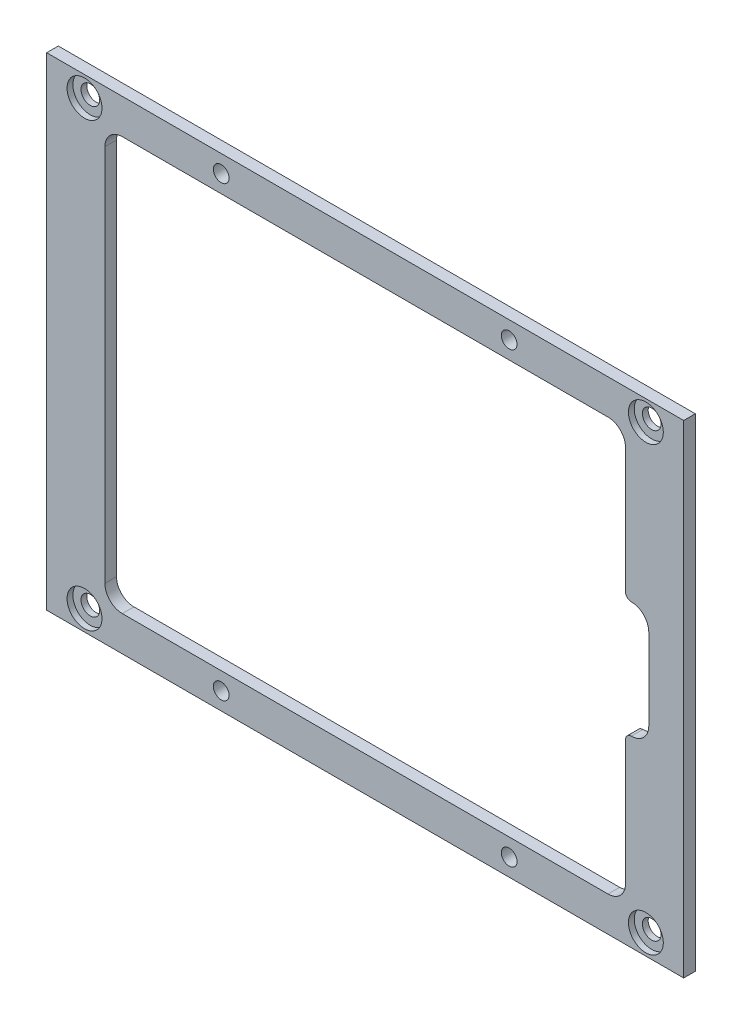
SolidWorks part; units mm, degrees
ref_plane "Front Plane" through (0, 0, 0) normal (0, 0, 1) x (1, 0, 0)
ref_plane "Top Plane" through (0, 0, 0) normal (0, 1, 0) x (1, 0, 0)
ref_plane "Right Plane" through (0, 0, 0) normal (1, 0, 0) x (0, 0, -1)
sketch "Sketch1" plane through (0, 0, 7.4347) normal (0, 0, 1) x (1, 0, 0)
  line L0 (-55.4936, 6.4519) -> (-55.4936, 3.4519) construction
  line L1 (-55.4936, 3.4519) -> (54.0064, 3.4519)
  line L2 (-55.4936, 3.4519) -> (-55.4936, 86.4519)
  line L3 (-55.4936, 86.4519) -> (54.0064, 86.4519)
  line L4 (54.0064, 3.4519) -> (54.0064, 86.4519)
  line L5 (55.0064, 3.4519) -> (-56.4936, 3.4519) construction
  line L6 (-51.4936, 3.4519) -> (-51.4936, 86.4519) construction
  line L7 (-42.4936, 80.4519) -> (41.0064, 80.4519)
  line L8 (-45.4936, 77.4519) -> (-45.4936, 12.4519)
  line L9 (-42.4936, 9.4519) -> (41.0064, 9.4519)
  line L10 (44.0064, 77.4519) -> (44.0064, 54.9519)
  line L11 (54.0064, 44.9519) -> (44.0064, 44.9519) construction
  line L12 (44.0064, 54.9519) -> (48.0064, 54.9519)
  line L14 (44.0064, 34.9519) -> (48.0064, 34.9519)
  line L15 (48.0064, 54.9519) -> (48.0064, 44.9519)
  line L16 (48.0064, 44.9519) -> (48.0064, 34.9519)
  line L17 (44.0064, 34.9519) -> (44.0064, 12.4519)
  arc A0 (-45.4936, 12.4519) -> (-42.4936, 9.4519) centre (-42.4936, 12.4519) ccw
  arc A1 (41.0064, 9.4519) -> (44.0064, 12.4519) centre (41.0064, 12.4519) ccw
  arc A2 (41.0064, 80.4519) -> (44.0064, 77.4519) centre (41.0064, 77.4519) cw
  arc A3 (-42.4936, 80.4519) -> (-45.4936, 77.4519) centre (-42.4936, 77.4519) ccw
  dimension "D7" = 3
  dimension "D1" = 109.5
  dimension "D2" = 83
  dimension "D3" = 6
  dimension "D4" = 6
  dimension "D5" = 6
  dimension "D6" = 6
  dimension "D8" = 10
  dimension "D9" = 10
  dimension "D10" = 4
extrude "Boss-Extrude1" add sketch "Sketch1" along normal blind 2
hole_wizard "Ø3.2 (3.2) Diameter Hole1" positions "Sketch7" profile "Sketch6" hole size "Ø3.2" standard "Ansi Metric" end condition up to next
sketch "Sketch7" plane through (0, 0, 9.4347) normal (0, 0, 1) x (1, 0, 0)
  line L0 (-55.4936, 3.4519) -> (54.0064, 3.4519) construction
  line L1 (-55.4936, 86.4519) -> (-55.4936, 3.4519) construction
  line L2 (54.0064, 86.4519) -> (-55.4936, 86.4519) construction
  line L3 (54.0064, 3.4519) -> (54.0064, 86.4519) construction
  point P0 (-48.9936, 6.9519)
  point P7 (-48.9936, 82.9519)
  point P9 (47.5064, 82.9519)
  point P11 (47.5064, 6.9519)
  dimension "D1" = 3.5
  dimension "D2" = 6.5
  dimension "D3" = 6.5
  dimension "D4" = 3.5
  dimension "D5" = 3.5
  dimension "D6" = 6.5
  dimension "D7" = 6.5
  dimension "D8" = 3.5
sketch "Sketch6" plane through (-48.9936, 6.9519, 9.4347) normal (1, 0, 0) x (0, -1, 0)
  line L0 (0, 0) -> (0, 2)
  line L1 (0, 2) -> (1.6, 2)
  line L2 (1.6, 2) -> (1.6, 0)
  line L5 (1.6, 0) -> (0, 0)
  line L11 (0, -6.35) -> (0, 107.95) construction
  dimension "Thru Hole Dia." = 3.2
  dimension "Thru Hole Depth" = 2
hole_wizard "Ø2.7 (2.7) Diameter Hole1" positions "3DSketch4" profile "Sketch11" hole size "Ø2.7" standard "Ansi Metric" end condition up to next
sketch3d "3DSketch4"
  line L0 (54.0064, 86.4519, 9.4347) -> (-55.4936, 86.4519, 9.4347) construction
  line L1 (-55.4936, 86.4519, 9.4347) -> (-55.4936, 3.4519, 9.4347) construction
  line L2 (54.0064, 3.4519, 9.4347) -> (54.0064, 86.4519, 9.4347) construction
  line L3 (-55.4936, 3.4519, 9.4347) -> (54.0064, 3.4519, 9.4347) construction
  point P0 (-25.4936, 83.4519, 9.4347)
  point P2 (24.0064, 83.4519, 9.4347)
  point P4 (24.0064, 6.4519, 9.4347)
  point P6 (-25.4936, 6.4519, 9.4347)
  dimension "D1" = 3
  dimension "D2" = 30
  dimension "D3" = 3
  dimension "D4" = 30
  dimension "D5" = 3
  dimension "D6" = 30
  dimension "D7" = 3
  dimension "D8" = 30
sketch "Sketch11" plane through (-25.4936, 83.4519, 9.4347) normal (1, 0, 0) x (0, -1, 0)
  line L0 (0, 0) -> (0, 2)
  line L1 (0, 2) -> (1.35, 2)
  line L2 (1.35, 2) -> (1.35, 0)
  line L5 (1.35, 0) -> (0, 0)
  line L11 (0, -6.35) -> (0, 107.95) construction
  dimension "Thru Hole Dia." = 2.7
  dimension "Thru Hole Depth" = 2
sketch "Sketch12" plane through (0, 0, 9.4347) normal (0, 0, 1) x (1, 0, 0)
  circle A0 centre (-48.9936, 82.9519) radius 3
  circle A1 centre (47.5064, 82.9519) radius 3
  circle A2 centre (47.5064, 6.9519) radius 3
  circle A3 centre (-48.9936, 6.9519) radius 3
  dimension "D1" = 6
  dimension "D2" = 6
  dimension "D3" = 6
  dimension "D4" = 6
extrude "Cut-Extrude1" cut sketch "Sketch12" against normal blind 1
fillet "Fillet1" radius 3 2 edges at (48.0064, 34.9519, 8.4347) (48.0064, 54.9519, 8.4347)
fillet "Fillet2" radius 1 2 edges at (44.0064, 34.9519, 8.4347) (44.0064, 54.9519, 8.4347)
